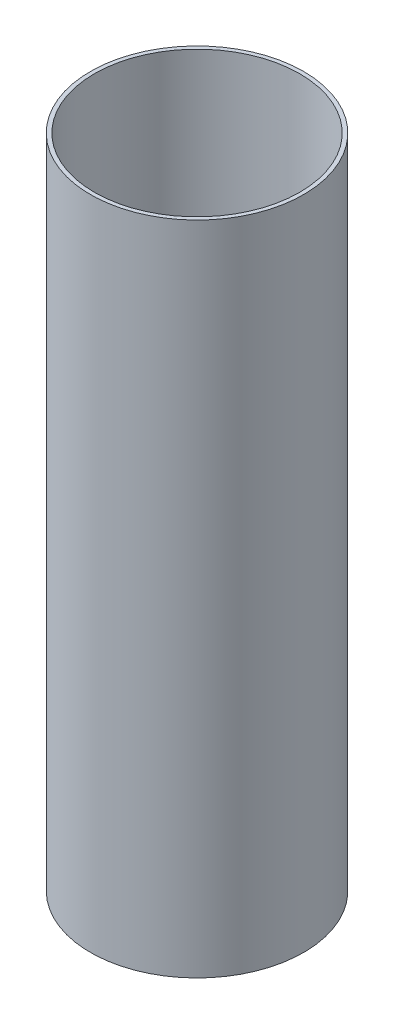
SolidWorks part; units mm, degrees
ref_plane "Front Plane" through (0, 0, 0) normal (0, 0, 1) x (1, 0, 0)
ref_plane "Top Plane" through (0, 0, 0) normal (0, 1, 0) x (1, 0, 0)
ref_plane "Right Plane" through (0, 0, 0) normal (1, 0, 0) x (0, 0, -1)
sketch "Sketch1" plane through (0, 0, 0) normal (0, 1, 0) x (1, 0, 0)
  circle A0 centre (0, 0) radius 49.5173
  circle A1 centre (0, 0) radius 47.6885
  dimension "D1" = 99.0346
  dimension "D2" = 95.377
extrude "Boss-Extrude1" add sketch "Sketch1" along normal blind 304.8
equation "\"Coupler_OD\" = 3.899in"
equation "\"Coupler_ID\" = 3.755in"
equation "\"Mid_Coupler_Length\" = 12in"
equation "\"D1@Sketch1\"=\"Coupler_OD\""
equation "\"D2@Sketch1\"=\"Coupler_ID\""
equation "\"D1@Boss-Extrude1\"=\"Mid_Coupler_Length\""
